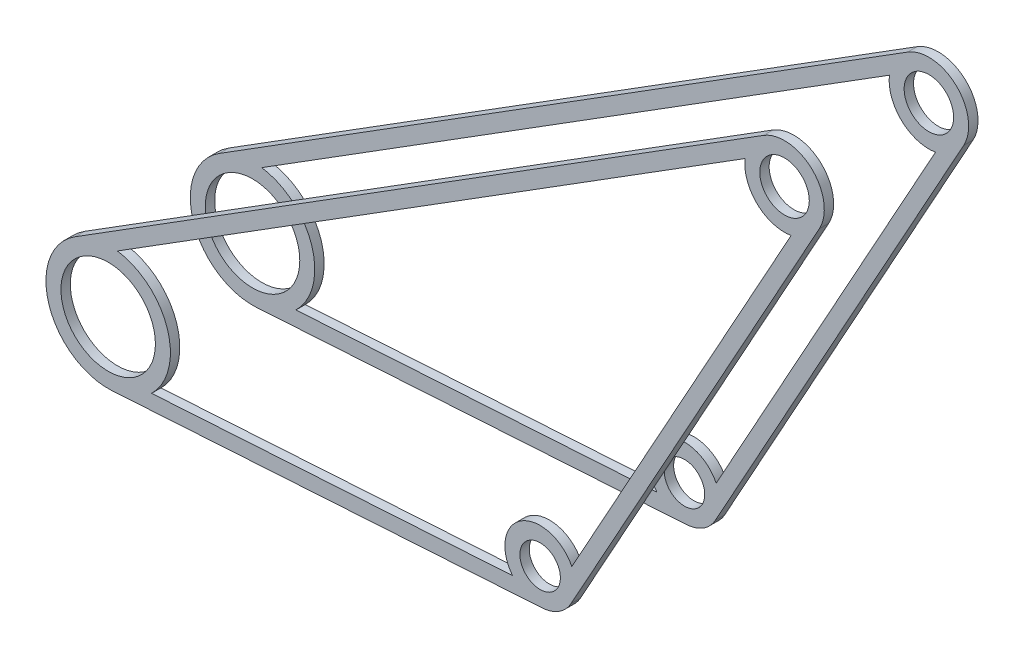
SolidWorks part; units mm, degrees
ref_plane "Front Plane" through (0, 0, 0) normal (0, 0, 1) x (1, 0, 0)
ref_plane "Top Plane" through (0, 0, 0) normal (0, 1, 0) x (1, 0, 0)
ref_plane "Right Plane" through (0, 0, 0) normal (1, 0, 0) x (0, 0, -1)
sketch "Sketch1" plane through (0, 0, 0) normal (0, 0, 1) x (1, 0, 0)
  line L0 (0, 0) -> (73.152, 0) construction
  line L1 (73.152, 0) -> (114.5399, 76.3747) construction
  line L2 (114.5399, 76.3747) -> (0, 0) construction
  line L3 (-5.6029, 8.9286) -> (110.9621, 82.0761)
  line L4 (120.4295, 73.1159) -> (78.3748, -2.8898)
  line L5 (73.5251, -5.9573) -> (0.6588, -10.5204)
  line L6 (-4.2528, 6.7771) -> (112.3122, 79.9246)
  line L7 (0.5001, -7.9854) -> (73.3663, -3.4223)
  line L8 (76.1523, -1.6601) -> (118.207, 74.3457)
  circle A0 centre (0, 0) radius 8.001
  circle A1 centre (73.152, 0) radius 3.429
  circle A2 centre (114.5399, 76.3747) radius 4.191
  circle A3 centre (0, 0) radius 10.541
  circle A4 centre (73.152, 0) radius 5.969
  circle A5 centre (114.5399, 76.3747) radius 6.731
  dimension "D1" = 8.382
  dimension "D2" = 6.858
  dimension "D3" = 16.002
  dimension "D6" = 2.54
  dimension "D7" = 2.54
  dimension "D8" = 2.54
  dimension "D4" = 73.152
  dimension "D5" = 86.868
  dimension "D9" = 137.668
extrude "Boss-Extrude1" add sketch "Sketch1" along normal blind 1.5875 from offset 11.43 contours A5 L3 A3 L6 | L6 A3 A0 | A4 A3 L5 | A4 L8 A1 | A5 L8 A4 L4 | A5 L6 A2 L8 | A3 L6 A0 | L8 A4 A1 | L6 A5 L8 A2 region at (-2.0989, 10.0476, 0) region at (53.7785, 44.7109, 0) region at (117.7058, 82.0991, 0) region at (37.6389, -6.9621, 0) region at (7.8072, 6.7258, 0) region at (111.5933, 73.2613, 0) region at (75.1084, -3.0932, 0) region at (98.251, 35.6128, 0) region at (70.041, 4.9185, 0)
extrude "Boss-Extrude2" add sketch "Sketch1<4>" against normal blind 1.5875 from offset 11.43 separate body contours A5 L3 A3 L6 | L6 A3 A0 | A3 L6 A0 | A4 A3 L5 | A4 L8 A1 | L8 A4 A1 | A5 L8 A4 L4 | L6 A5 L8 A2 | A5 L6 A2 L8 region at (-2.0989, 10.0476, 0) region at (53.7785, 44.7109, 0) region at (117.7058, 82.0991, 0) region at (37.6389, -6.9621, 0) region at (7.8072, 6.7258, 0) region at (111.5933, 73.2613, 0) region at (75.1084, -3.0932, 0) region at (98.251, 35.6128, 0) region at (70.041, 4.9185, 0) offset against normal yes
sketch "Sketch1<4>" plane through (0, 0, 0) normal (0, 0, 1) x (1, 0, 0) same geometry as "Sketch1"
equation "\"D19@Boss-Extrude2\"=.45"
